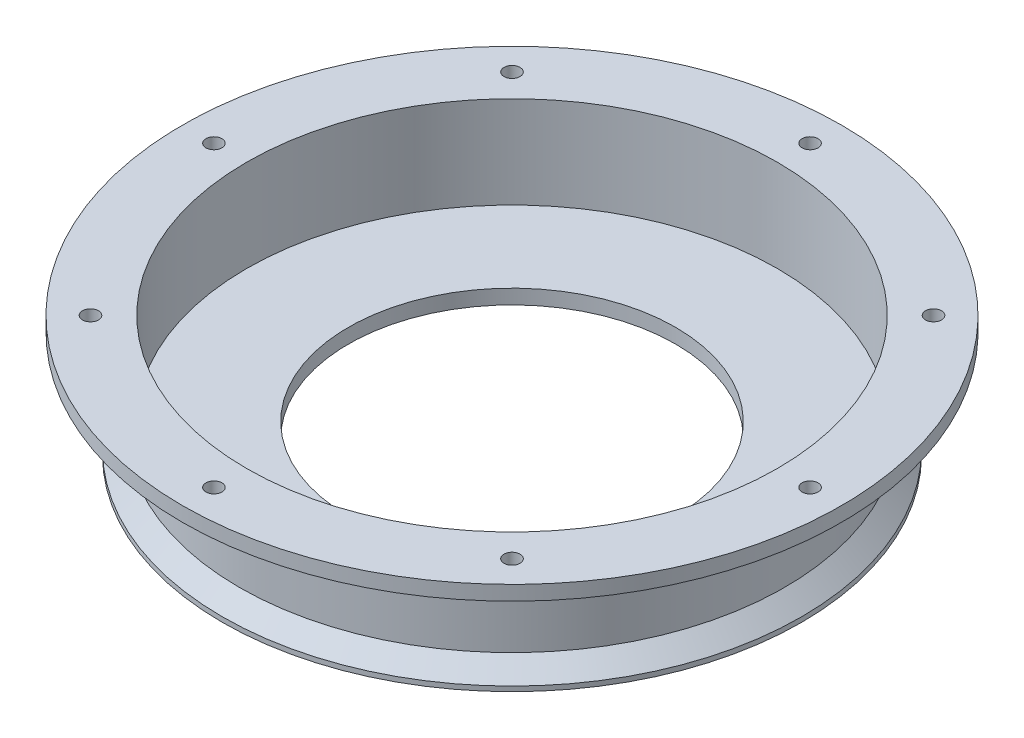
SolidWorks part; units mm, degrees
material "7050-T73510"
ref_plane "正面" through (0, 0, 0) normal (0, 0, 1) x (1, 0, 0)
ref_plane "平面" through (0, 0, 0) normal (0, 1, 0) x (1, 0, 0)
ref_plane "右側面" through (0, 0, 0) normal (1, 0, 0) x (0, 0, -1)
ref_axis "中心" through (0, 100.8172, 0) along (0, -1, 0)
sketch "ｽｹｯﾁ1" plane through (0, 0, 0) normal (0, 0, 1) x (1, 0, 0)
  line L0 (-109.5, 26.8454) -> (-136, 26.8454)
  line L1 (-136, 26.8454) -> (-136, 20.8454)
  line L2 (-136, 20.8454) -> (-112.5, 20.8454)
  line L3 (-112.5, 20.8454) -> (-112.5, -14.1546)
  line L4 (-112.5, -14.1546) -> (-119.5, -21.1546)
  line L5 (-119.5, -21.1546) -> (-119.5, -23.1546)
  line L6 (-119.5, -23.1546) -> (-110, -23.1546)
  line L7 (-110, -23.1546) -> (-104, -17.1546)
  line L8 (-104, -17.1546) -> (-67.5, -17.1546)
  line L9 (-67.5, -17.1546) -> (-67.5, -11.1546)
  line L10 (-67.5, -11.1546) -> (-109.5, -11.1546)
  line L11 (-109.5, -11.1546) -> (-109.5, 26.8454)
  line L13 (0, 35.1784) -> (0, -27.1557) construction
  dimension "D1" = 109.5
  dimension "D2" = 112.5
  dimension "D3" = 136
  dimension "D4" = 6
  dimension "D5" = 50
  dimension "D6" = 67.5
  dimension "D7" = 119.5
  dimension "D8" = 110
  dimension "D9" = 6
  dimension "D10" = 2
  dimension "D11" = 135
  dimension "D12" = 135
revolve "回転1" add sketch "ｽｹｯﾁ1" angle 360 about axis through (0, 100.8172, 0) along (0, -1, 0)
sketch "ｽｹｯﾁ2" plane through (0, 20.8454, 0) normal (0, -1, 0) x (1, 0, 0)
  circle A0 centre (123, 0) radius 3.3
  dimension "D1" = 6.6
  dimension "D2" = 123
extrude "Base_Plateへの固定用穴(M6の六角ボルトを使用)" cut sketch "ｽｹｯﾁ2" against normal through all
pattern_circular "円形ﾊﾟﾀｰﾝ1" count 8 over 360 about axis through (0, 35.1784, 0) along (0, 1, 0) of "Base_Plateへの固定用穴(M6の六角ボルトを使用)"
sketch "ｽｹｯﾁ3" plane through (0, 20.8454, 0) normal (0, -1, 0) x (1, 0, 0)
  circle A0 centre (0, 123) radius 6
  dimension "D1" = 12
